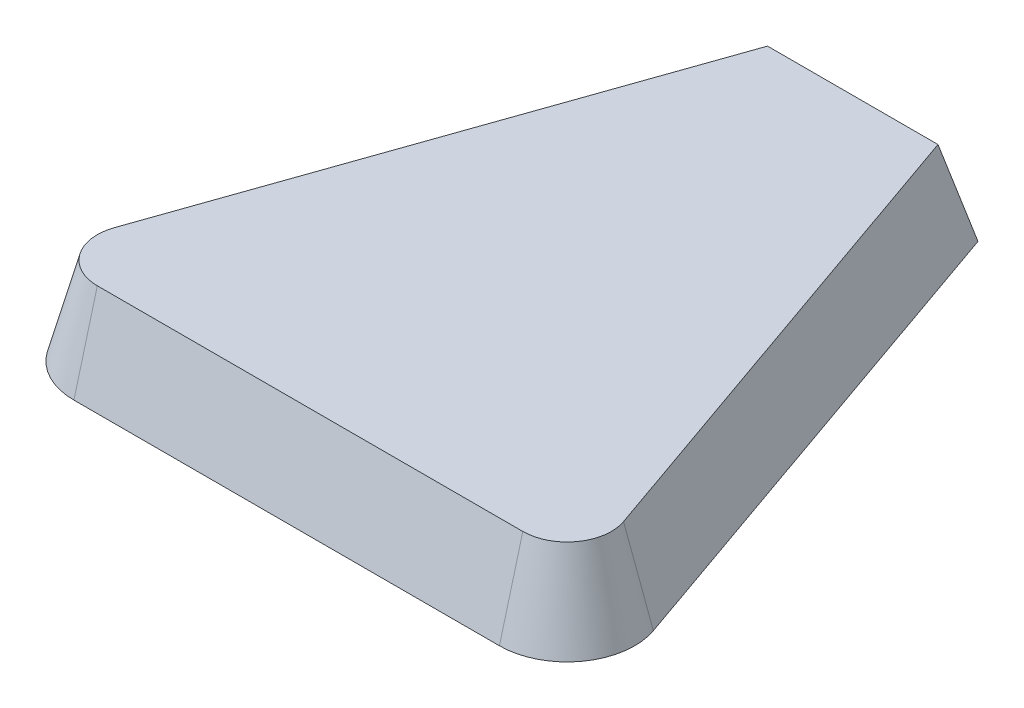
SolidWorks part; units mm, degrees
ref_plane "Front" through (0, 0, 0) normal (0, 0, 1) x (1, 0, 0)
ref_plane "Top" through (0, 0, 0) normal (0, 1, 0) x (1, 0, 0)
ref_plane "Right" through (0, 0, 0) normal (1, 0, 0) x (0, 0, -1)
sketch "Sketch2" plane through (0, 0, 0) normal (0, 1, 0) x (1, 0, 0)
  line L0 (0, 0) -> (45, 0)
  line L3 (-38.4052, -150) -> (83.4052, -150)
  line L5 (0, 0) -> (-47.8438, -136.6965)
  line L6 (45, 0) -> (92.8438, -136.6965)
  arc A0 (-47.8438, -136.6965) -> (-38.4052, -150) centre (-38.4052, -140) ccw
  arc A1 (83.4052, -150) -> (92.8438, -136.6965) centre (83.4052, -140) ccw
  point P8 (22.5, -150)
  dimension "D1" = 45
  dimension "D3" = 150
extrude "Boss-Extrude1" add sketch "Sketch2" along normal blind 25
ref_plane "Plane3" through (0, 35, 0) normal (0, 1, 0) x (1, 0, 0)
draft "Draft8" type of draft neutral plane draft angle 15 neutral plane "Plane3" faces to draft 6 face at (22.5, 12.5, 0) face at (-44.8427, 12.5, 144.5673) face at (89.8427, 12.5, 144.5673) face at (68.9219, 12.5, 68.3482) face at (22.5, 12.5, 150) face at (-23.9219, 12.5, 68.3482) neutral plane through (0, 35, 0) neutral plane normal (0, 1, 0) parameters "D1"=15
shell "Shell1" thickness 5 removed face at (22.5, 0, 96.1077)
